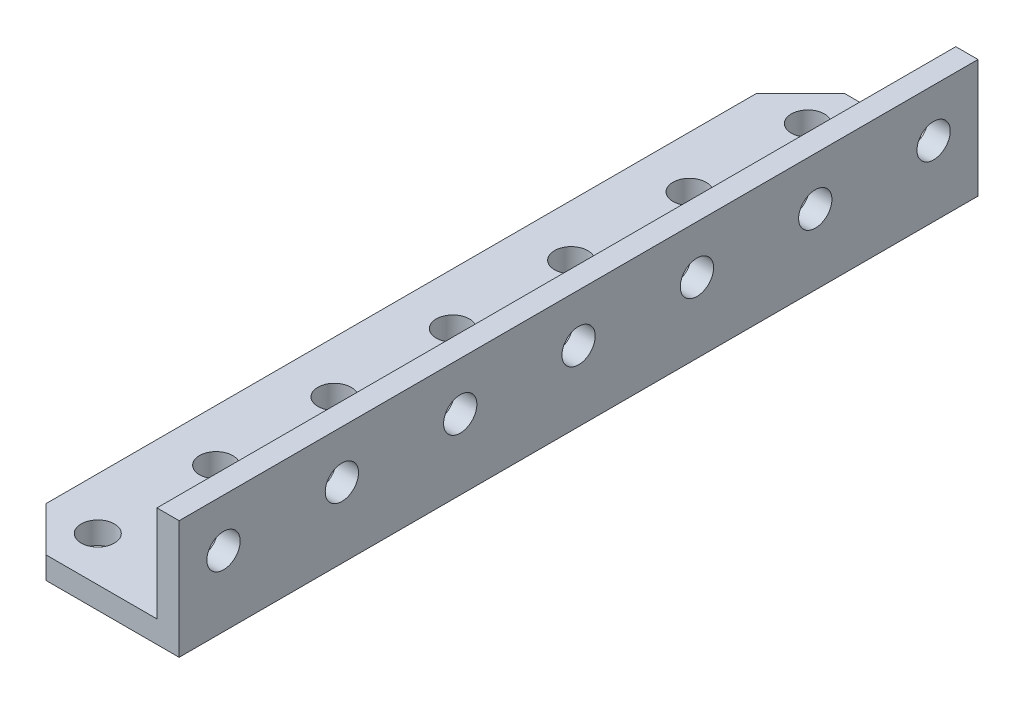
SolidWorks part; units mm, degrees
ref_plane "Front Plane" through (0, 0, 0) normal (0, 0, 1) x (1, 0, 0)
ref_plane "Top Plane" through (0, 0, 0) normal (0, 1, 0) x (1, 0, 0)
ref_plane "Right Plane" through (0, 0, 0) normal (1, 0, 0) x (0, 0, -1)
sketch "Sketch1" plane through (0, 0, 0) normal (0, 0, 1) x (1, 0, 0)
  line L0 (0, 0) -> (38.1, 0)
  line L1 (38.1, 0) -> (38.1, 25.4)
  line L2 (38.1, 25.4) -> (33.3375, 25.4)
  line L3 (33.3375, 25.4) -> (33.3375, 4.7625)
  line L4 (33.3375, 4.7625) -> (0, 4.7625)
  line L5 (0, 4.7625) -> (0, 0)
  dimension "D1" = 38.1
  dimension "D2" = 25.4
  dimension "D3" = 4.7625
extrude "Boss-Extrude1" add sketch "Sketch1" along normal blind 177.8 contours L4 L5 L0 L1 L2 L3
sketch "Sketch6" plane through (0, 4.7625, 0) normal (0, 1, 0) x (1, 0, 0)
  line L0 (11.1125, -177.8) -> (11.1125, 0) construction
  line L1 (33.3375, -177.8) -> (0, -177.8) construction
  line L2 (33.3375, 0) -> (0, 0) construction
  line L5 (33.3375, -177.8) -> (33.3375, 0) construction
  line L6 (11.1125, -165.1) -> (11.1125, -139.7) construction
  point P8 (11.1125, -165.1)
  point P38 (11.1125, -139.7)
  point P39 (11.1125, -114.3)
  point P40 (11.1125, -88.9)
  point P41 (11.1125, -63.5)
  point P42 (11.1125, -38.1)
  point P43 (11.1125, -12.7)
  dimension "D1" = 22.225
  dimension "D2" = 12.7
  dimension "D4" = 25.4
  dimension "D3" = 7
hole_wizard "1/4 Clearance Hole1" positions "Sketch6" profile "Sketch7" hole size "1/4" standard "ANSI Inch" end condition up to next
sketch "Sketch7" plane through (11.1125, 4.7625, 12.7) normal (1, 0, 0) x (0, 0, 1)
  line L0 (0, 0) -> (0, 4.7625)
  line L1 (0, 4.7625) -> (3.5712, 4.7625)
  line L2 (3.5712, 4.7625) -> (3.5712, 0)
  line L5 (3.5712, 0) -> (0, 0)
  line L11 (0, -6.35) -> (0, 107.95) construction
  dimension "Thru Hole Dia." = 7.1425
  dimension "Thru Hole Depth" = 4.7625
sketch "Sketch8" plane through (33.3375, 0, 0) normal (-1, 0, 0) x (0, 0, 1)
  line L0 (0, 15.0812) -> (177.8, 15.0812) construction
  line L1 (0, 25.4) -> (0, 4.7625) construction
  line L2 (177.8, 25.4) -> (177.8, 4.7625) construction
  line L4 (12.7, 15.0812) -> (38.1, 15.0812) construction
  point P6 (12.7, 15.0812)
  point P26 (38.1, 15.0812)
  point P27 (63.5, 15.0812)
  point P28 (88.9, 15.0812)
  point P29 (114.3, 15.0812)
  point P30 (139.7, 15.0812)
  point P31 (165.1, 15.0812)
  point P32 (190.5, 15.0812)
  dimension "D1" = 12.7
  dimension "D3" = 25.4
  dimension "D2" = 8
hole_wizard "1/4 Clearance Hole2" positions "Sketch8" profile "Sketch9" hole size "1/4" standard "ANSI Inch" end condition up to next
sketch "Sketch9" plane through (33.3375, 15.0812, 190.5) normal (0, 1, 0) x (0, 0, 1)
  line L0 (0, 0) -> (0, 4.7625)
  line L1 (0, 4.7625) -> (3.5712, 4.7625)
  line L2 (3.5712, 4.7625) -> (3.5712, 0)
  line L5 (3.5712, 0) -> (0, 0)
  line L11 (0, -6.35) -> (0, 107.95) construction
  dimension "Thru Hole Dia." = 7.1425
  dimension "Thru Hole Depth" = 4.7625
chamfer "Chamfer1" distance 12.7 angle 45 2 edges at (0, 2.3813, 177.8) (0, 2.3813, 0)
ref_plane "Plane1" through (0, 0, 88.9) normal (0, 0, -1) x (-1, 0, 0)
sketch "Sketch10" plane through (0, 0, 0) normal (0, 0, -1) x (-1, 0, 0)
  line L1 (-38.1, 25.4) -> (0, 25.4)
  line L2 (-38.1, 25.4) -> (-38.1, 0)
  line L3 (-38.1, 0) -> (0, 0)
  line L4 (0, 25.4) -> (0, 0)
extrude "Cut-Extrude1" cut sketch "Sketch10" against normal blind 3.175
mirror "Mirror1" about plane through (0, 0, 88.9) normal (0, 0, -1) of "Cut-Extrude1"
